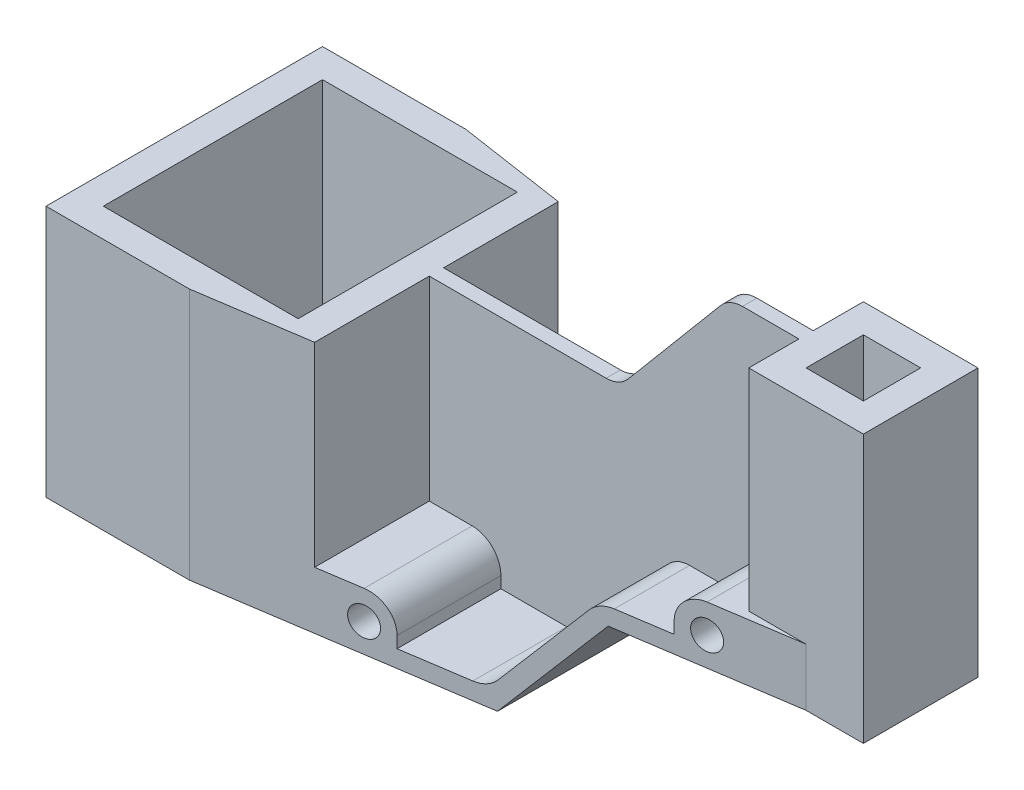
SolidWorks part; units mm, degrees
material "1060 Alloy"
ref_plane "Front Plane" through (0, 0, 0) normal (0, 0, 1) x (1, 0, 0)
ref_plane "Top Plane" through (0, 0, 0) normal (0, 1, 0) x (1, 0, 0)
ref_plane "Right Plane" through (0, 0, 0) normal (1, 0, 0) x (0, 0, -1)
sketch "Sketch1" plane through (0, 0, 0) normal (0, 0, 1) x (1, 0, 0)
  line L1 (-34.5107, 107.7078) -> (222.4893, 107.7078)
  line L2 (-34.5107, 107.7078) -> (-34.5107, -25.7922)
  line L3 (-34.5107, -25.7922) -> (222.4893, -25.7922)
  line L4 (222.4893, 107.7078) -> (222.4893, -25.7922)
extrude "Boss-Extrude1" add sketch "Sketch1" along normal blind 96.5
sketch "Sketch2" plane through (0, 0, 96.5) normal (0, 0, 1) x (1, 0, 0)
  line L5 (-34.5107, 107.7078) -> (78.4893, 107.7078)
  line L6 (-34.5107, 107.7078) -> (-34.5107, 62.2078)
  line L7 (-34.5107, 62.2078) -> (78.4893, 62.2078)
  line L8 (78.4893, 107.7078) -> (78.4893, 62.2078)
  line L9 (222.4893, -25.7922) -> (142.4893, -25.7922)
  line L10 (222.4893, -25.7922) -> (222.4893, 14.2078)
  line L11 (222.4893, 14.2078) -> (142.4893, 14.2078)
  line L12 (142.4893, -25.7922) -> (142.4893, 14.2078)
extrude "Cut-Extrude1" cut sketch "Sketch2" against normal blind 96.5
sketch "Sketch4" plane through (0, 62.2078, 0) normal (0, 1, 0) x (1, 0, 0)
  line L5 (-34.5107, -96.5) -> (78.4893, -96.5) construction
  line L6 (-34.5107, 0) -> (53.4893, 0)
  line L7 (-34.5107, 0) -> (-34.5107, -48.25)
  line L9 (53.4893, 0) -> (53.4893, -48.25)
  line L11 (-34.5107, -48.25) -> (-34.5107, -96.5)
  line L12 (-34.5107, -96.5) -> (53.4893, -96.5)
  line L13 (53.4893, -48.25) -> (53.4893, -96.5)
  line L14 (-24.5107, -10) -> (-24.5107, -48.25)
  line L15 (-24.5107, -48.25) -> (-24.5107, -86.5)
  line L16 (-24.5107, -86.5) -> (43.4893, -86.5)
  line L17 (43.4893, -48.25) -> (43.4893, -86.5)
  line L18 (43.4893, -10) -> (43.4893, -48.25)
  line L19 (-24.5107, -10) -> (43.4893, -10)
  point P16 (9.4893, -96.5)
  dimension "D1" = 48.25
  dimension "D2" = 48.25
  dimension "D3" = 88
  dimension "D5" = 10
  dimension "D6" = 10
  dimension "D7" = 44
  dimension "D4" = 10
extrude "Cut-Extrude2" cut sketch "Sketch4" against normal blind 88 contours L14 L15 L16 L17 L18 L19
sketch "Sketch6" plane through (0, 107.7078, 0) normal (0, 1, 0) x (1, 0, 0)
  line L1 (222.4893, -96.5) -> (222.4893, 0) construction
  line L2 (222.4893, -28.25) -> (222.4893, 0)
  line L3 (222.4893, 0) -> (78.4893, 0) construction
  line L4 (222.4893, 0) -> (202.4893, 0)
  line L5 (202.4893, 0) -> (202.4893, -28.25)
  line L6 (202.4893, -28.25) -> (222.4893, -28.25)
  line L7 (222.4893, -96.5) -> (222.4893, -68.25)
  line L8 (222.4893, -68.25) -> (202.4893, -68.25)
  line L9 (202.4893, -68.25) -> (202.4893, -96.5)
  line L10 (222.4893, -96.5) -> (78.4893, -96.5) construction
  line L11 (202.4893, -96.5) -> (222.4893, -96.5)
extrude "Cut-Extrude3" cut sketch "Sketch6" against normal blind 93.5
sketch "Sketch7" plane through (0, 107.7078, 0) normal (0, 1, 0) x (1, 0, 0)
  line L0 (202.4893, -28.25) -> (202.4893, 0)
  line L1 (202.4893, 0) -> (78.4893, 0)
  line L2 (78.4893, 0) -> (78.4893, -28.25)
  line L3 (78.4893, 0) -> (78.4893, -96.5) construction
  line L4 (78.4893, -28.25) -> (202.4893, -28.25)
  line L5 (202.4893, -68.25) -> (78.4893, -68.25)
  line L6 (78.4893, -68.25) -> (78.4893, -96.5)
  line L7 (78.4893, -96.5) -> (202.4893, -96.5)
  line L8 (202.4893, -96.5) -> (202.4893, -68.25)
extrude "Cut-Extrude4" cut sketch "Sketch7" against normal blind 73.5
sketch "Sketch8" plane through (0, 107.7078, 0) normal (0, 1, 0) x (1, 0, 0)
  line L1 (78.4893, -28.25) -> (222.4893, -28.25) construction
  line L5 (78.4893, -28.25) -> (78.4893, -68.25) construction
  line L13 (182.4893, -28.25) -> (78.4893, -28.25)
  line L14 (182.4893, -28.25) -> (182.4893, -45.75)
  line L15 (182.4893, -45.75) -> (78.4893, -45.75)
  line L16 (78.4893, -28.25) -> (78.4893, -45.75)
  line L17 (222.4893, -68.25) -> (78.4893, -68.25) construction
  line L18 (182.4893, -68.25) -> (78.4893, -68.25)
  line L19 (182.4893, -68.25) -> (182.4893, -50.75)
  line L20 (182.4893, -50.75) -> (78.4893, -50.75)
  line L21 (78.4893, -68.25) -> (78.4893, -50.75)
extrude "Cut-Extrude5" cut sketch "Sketch8" against normal blind 73.5
sketch "Sketch9" plane through (0, 62.2078, 0) normal (0, 1, 0) x (1, 0, 0)
  line L0 (-34.5107, -96.5) -> (78.4893, -96.5) construction
  line L1 (78.4893, -50.75) -> (53.4893, -50.75)
  line L2 (78.4893, -50.75) -> (78.4893, -96.5)
  line L3 (78.4893, -96.5) -> (53.4893, -96.5)
  line L4 (53.4893, -50.75) -> (53.4893, -96.5)
  line L5 (-34.5107, 0) -> (78.4893, 0) construction
  line L6 (78.4893, -45.75) -> (53.4893, -45.75)
  line L7 (78.4893, -45.75) -> (78.4893, 0)
  line L8 (78.4893, 0) -> (53.4893, 0)
  line L9 (53.4893, -45.75) -> (53.4893, 0)
extrude "Cut-Extrude6" cut sketch "Sketch9" against normal blind 68
sketch "Sketch11" plane through (0, 34.2078, 0) normal (0, 1, 0) x (1, 0, 0)
  line L0 (78.4893, -96.5) -> (202.4893, -96.5) construction
  line L6 (78.4893, -50.75) -> (162.4893, -50.75)
  line L7 (78.4893, -50.75) -> (78.4893, -96.5)
  line L8 (78.4893, -96.5) -> (162.4893, -96.5)
  line L9 (162.4893, -50.75) -> (162.4893, -96.5)
extrude "Cut-Extrude7" cut sketch "Sketch11" against normal blind 14 contours L7 L6 L9 L8
sketch "Sketch12" plane through (0, 34.2078, 0) normal (0, 1, 0) x (1, 0, 0)
  line L0 (202.4893, 0) -> (78.4893, 0) construction
  line L6 (78.4893, 0) -> (162.4893, 0)
  line L7 (78.4893, 0) -> (78.4893, -45.75)
  line L8 (78.4893, -45.75) -> (162.4893, -45.75)
  line L9 (162.4893, 0) -> (162.4893, -45.75)
extrude "Cut-Extrude8" cut sketch "Sketch12" against normal blind 14 contours L7 L6 L9 L8
sketch "Sketch13" plane through (0, 0, 96.5) normal (0, 0, 1) x (1, 0, 0)
  line L0 (142.4893, 14.2078) -> (108.9253, -25.7922)
  line L3 (139.6915, 20.2078) -> (106.1275, -19.7922)
  line L4 (-34.5107, -25.7922) -> (142.4893, -25.7922) construction
  line L5 (139.6915, 20.2078) -> (78.4893, 20.2078)
  line L6 (78.4893, 20.2078) -> (162.4893, 20.2078) construction
  line L7 (78.4893, 20.2078) -> (78.4893, -19.7922)
  line L8 (78.4893, -19.7922) -> (106.1275, -19.7922)
  dimension "D1" = 6
  dimension "D2" = 130
  dimension "D3" = 6
extrude "Cut-Extrude10" cut sketch "Sketch13" against normal blind 45.75 contours L8 L3 L5 L7
sketch "Sketch15" plane through (0, 0, 96.5) normal (0, 0, 1) x (1, 0, 0)
  line L0 (142.4893, 14.2078) -> (108.9253, -25.7922)
  line L1 (-34.5107, -25.7922) -> (142.4893, -25.7922) construction
  line L2 (139.6915, 20.2078) -> (106.1275, -19.7922) construction
  line L3 (142.4893, 14.2078) -> (142.4893, -25.7922)
  line L4 (142.4893, -25.7922) -> (108.9253, -25.7922)
  dimension "D1" = 6
extrude "Cut-Extrude11" cut sketch "Sketch15" against normal blind 96.5 contours L4 L0 L3
sketch "Sketch16" plane through (0, 0, 0) normal (0, 0, -1) x (-1, 0, 0)
  line L0 (-78.4893, -5.7922) -> (-78.4893, -19.7922)
  line L1 (-78.4893, -19.7922) -> (-106.1275, -19.7922)
  line L2 (-106.1275, -19.7922) -> (-139.6915, 20.2078)
  line L3 (-78.4893, 20.2078) -> (-162.4893, 20.2078) construction
  line L4 (-139.6915, 20.2078) -> (-78.4893, 20.2078)
  line L5 (-78.4893, 20.2078) -> (-78.4893, -19.7922)
  line L6 (34.5107, -25.7922) -> (-108.9253, -25.7922) construction
  line L8 (-142.4893, 14.2078) -> (-108.9253, -25.7922)
  dimension "D1" = 6
  dimension "D2" = 6
  dimension "D3" = 130
extrude "Cut-Extrude12" cut sketch "Sketch16" against normal blind 45.75 contours L1 L2 L4 L5
sketch "Sketch17" plane through (0, 0, 50.75) normal (0, 0, 1) x (1, 0, 0)
  line L6 (78.4893, 62.2078) -> (119.8621, 62.2078)
  line L7 (119.8621, 62.2078) -> (158.1482, 107.7078)
  line L8 (182.4893, 107.7078) -> (78.4893, 107.7078) construction
  line L9 (158.1482, 107.7078) -> (78.4893, 107.7078)
  line L10 (78.4893, 107.7078) -> (78.4893, 62.2078)
  line L11 (139.6915, 20.2078) -> (106.1275, -19.7922) construction
  point P2 (122.9095, 0.2078)
  dimension "D1" = 42.25
extrude "Cut-Extrude13" cut sketch "Sketch17" against normal blind 5
sketch "Sketch18" plane through (0, 0, 96.5) normal (0, 0, 1) x (1, 0, 0)
  circle A0 centre (172.4893, 24.2078) radius 5
  circle A1 centre (68.4893, -15.7922) radius 5
  point P0 (0, 0)
extrude "Cut-Extrude14" cut sketch "Sketch18" against normal blind 96.5
sketch "Sketch19" plane through (0, 107.7078, 0) normal (0, 1, 0) x (1, 0, 0)
  line L0 (212.4893, -38.25) -> (212.4893, -58.25)
  line L5 (212.4893, -58.25) -> (192.4893, -58.25)
  line L6 (192.4893, -38.25) -> (192.4893, -58.25)
  line L7 (212.4893, -38.25) -> (192.4893, -38.25)
extrude "Cut-Extrude15" cut sketch "Sketch19" against normal blind 93.5 contours L0 L5 L6 L7
sketch "Sketch51" plane through (0, 62.2078, 0) normal (0, 1, 0) x (1, 0, 0)
  line L0 (9.4893, -96.5) -> (15.4893, -96.5)
  line L1 (-34.5107, -96.5) -> (53.4893, -96.5) construction
  line L4 (15.4893, -96.5) -> (53.4893, -96.5)
  line L5 (53.4893, -96.5) -> (53.4893, -90.7594)
  line L6 (53.4893, -90.7594) -> (15.4893, -96.5)
extrude "Cut-Extrude42" cut sketch "Sketch51" against normal blind 88 contours L4 L5 L6
sketch "Sketch62" plane through (0, 14.2078, 0) normal (0, -1, 0) x (1, 0, 0)
  line L2 (142.4893, 96.5) -> (202.4893, 96.5)
  line L3 (202.4893, 96.5) -> (202.4893, 68.25)
  line L4 (142.4893, 96.5) -> (142.4893, 77.3142)
  line L5 (142.4893, 0) -> (142.4893, 96.5) construction
  line L6 (142.4893, 77.3142) -> (202.4893, 68.25)
extrude "Cut-Extrude53" cut sketch "Sketch62" against normal blind 20
sketch "Sketch75" plane through (0, -25.7922, 0) normal (0, -1, 0) x (1, 0, 0)
  line L0 (142.4893, 77.3142) -> (53.4893, 90.7594)
  line L2 (53.4893, 90.7594) -> (53.4893, 96.5)
  line L3 (53.4893, 96.5) -> (142.4893, 96.5)
  line L4 (142.4893, 96.5) -> (142.4893, 77.3142)
extrude "Cut-Extrude61" cut sketch "Sketch75" against normal blind 50.68
sketch "Sketch79" plane through (0, 62.2078, 0) normal (0, 1, 0) x (1, 0, 0)
  line L1 (-34.5107, 0) -> (53.4893, 0) construction
  line L3 (15.4893, 0) -> (53.4893, 0)
  line L4 (53.4893, 0) -> (53.4893, -5.7406)
  line L5 (53.4893, 0) -> (53.4893, -45.75) construction
  line L6 (53.4893, -5.7406) -> (15.4893, 0)
extrude "Cut-Extrude62" cut sketch "Sketch79" against normal blind 88
sketch "Sketch80" plane through (0, -25.7922, 0) normal (0, -1, 0) x (1, 0, 0)
  line L1 (53.4893, 5.7406) -> (53.4893, 0)
  line L2 (53.4893, 0) -> (142.4893, 0)
  line L3 (142.4893, 0) -> (142.4893, 19.1858)
  line L4 (142.4893, 19.1858) -> (53.4893, 5.7406)
extrude "Cut-Extrude63" cut sketch "Sketch80" against normal blind 88
sketch "Sketch81" plane through (0, 14.2078, 0) normal (0, -1, 0) x (1, 0, 0)
  line L0 (142.4893, 19.1858) -> (202.4893, 28.25)
  line L1 (202.4893, 28.25) -> (202.4893, 0)
  line L2 (202.4893, 0) -> (142.4893, 0)
  line L3 (142.4893, 0) -> (142.4893, 19.1858)
extrude "Cut-Extrude64" cut sketch "Sketch81" against normal blind 88
fillet "Fillet2" radius 10 1 edges at (162.4893, 34.2078, 62.5214)
fillet "Fillet3" radius 10 1 edges at (162.4893, 34.2078, 33.9786)
fillet "Fillet4" radius 10 1 edges at (139.6915, 20.2078, 32.2566)
fillet "Fillet5" radius 10 1 edges at (139.6915, 20.2078, 64.2434)
fillet "Fillet6" radius 10 1 edges at (106.1275, -19.7922, 66.7787)
fillet "Fillet7" radius 10 1 edges at (106.1275, -19.7922, 29.7213)
fillet "Fillet8" radius 10 1 edges at (78.4893, -5.7922, 68.8663)
fillet "Fillet9" radius 10 1 edges at (78.4893, -5.7922, 27.6337)
fillet "Fillet10" radius 10 1 edges at (158.1482, 107.7078, 48.25)
fillet "Fillet11" radius 10 1 edges at (119.8621, 62.2078, 48.25)
